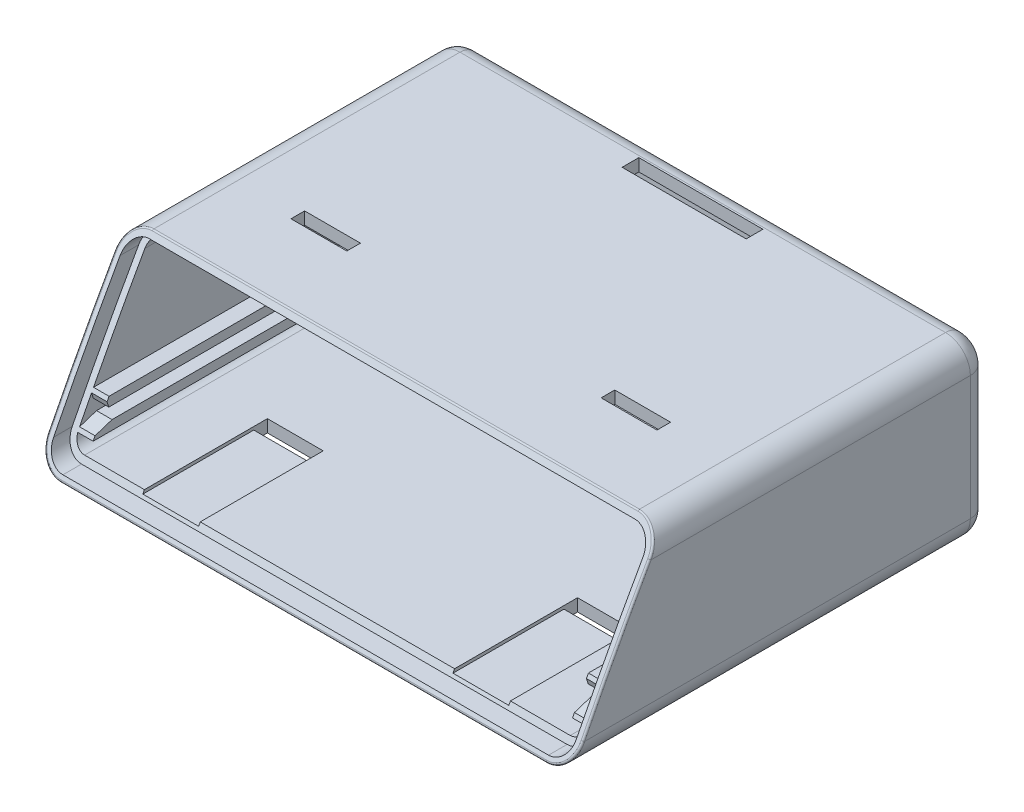
SolidWorks part; units mm, degrees
ref_plane "Front Plane" through (0, 0, 0) normal (0, 0, 1) x (1, 0, 0)
ref_plane "Top Plane" through (0, 0, 0) normal (0, 1, 0) x (1, 0, 0)
ref_plane "Right Plane" through (0, 0, 0) normal (1, 0, 0) x (0, 0, -1)
sketch "Sketch1" plane through (0, 0, 0) normal (0, 1, 0) x (1, 0, 0)
  line L1 (-43.14, -33.75) -> (43.14, -33.75)
  line L2 (-43.14, -33.75) -> (-43.14, 33.75)
  line L3 (-43.14, 33.75) -> (43.14, 33.75)
  line L4 (43.14, -33.75) -> (43.14, 33.75)
  line L5 (-43.14, -33.75) -> (43.14, 33.75) construction
  line L6 (-43.14, 33.75) -> (43.14, -33.75) construction
  point P0 (0, 0)
  dimension "D1" = 67.5
  dimension "D2" = 86.28
extrude "Boss-Extrude1" add sketch "Sketch1" along normal blind 28
fillet "Fillet1" radius 4 4 edges at (43.14, 28, 0) (43.14, 0, 0) (-43.14, 0, 0) (-43.14, 28, 0)
shell "Shell1" thickness 2
sketch "Sketch2" plane through (-43.14, 0, 0) normal (-1, 0, 0) x (0, 0, 1)
  line L0 (-33.75, 28) -> (33.75, 28) construction
  line L1 (18.75, 28) -> (33.75, 28)
  line L2 (33.75, 28) -> (33.75, 0)
  arc A0 (33.75, 0) -> (18.75, 28) centre (-392.2189, -210.1797) ccw
  dimension "D1" = 15
  dimension "D2" = 475
extrude "Cut-Extrude1" cut sketch "Sketch2" against normal through all
sketch "Sketch3" plane through (0, 0, -33.75) normal (0, 0, -1) x (-1, 0, 0)
  line L0 (-7.15, 18.7) -> (7.15, 18.7)
  line L1 (-6.95, 18.5) -> (6.95, 18.5) construction
  line L2 (-6.95, 18.5) -> (-6.95, 2.2) construction
  line L3 (-6.95, 2.2) -> (6.95, 2.2) construction
  line L4 (6.95, 18.5) -> (6.95, 2.2) construction
  line L5 (7.15, 18.7) -> (7.15, 2)
  line L6 (-7.15, 2) -> (7.15, 2)
  line L7 (-7.15, 18.7) -> (-7.15, 2)
  line L8 (27.25, 17.2) -> (38.3, 17.2)
  line L9 (27.45, 17) -> (38.1, 17) construction
  line L10 (27.45, 17) -> (27.45, 3.35) construction
  line L11 (27.45, 3.35) -> (38.1, 3.35) construction
  line L12 (38.1, 17) -> (38.1, 3.35) construction
  line L13 (38.3, 17.2) -> (38.3, 3.15)
  line L14 (27.25, 3.15) -> (38.3, 3.15)
  line L15 (27.25, 17.2) -> (27.25, 3.15)
  dimension "D1" = 0.2
  dimension "D2" = 0.2
extrude "Cut-Extrude2" cut sketch "Sketch3" against normal up to surface (2 mm away) up to face at (0, 14, -31.75)
fillet "Fillet2" radius 3 8 edges at (41.9684, 26.8284, -33.75) (43.14, 14, -33.75) (41.9684, 1.1716, -33.75) (0, 0, -33.75) (-41.9684, 1.1716, -33.75) (-43.14, 14, -33.75) (-41.9684, 26.8284, -33.75) (0, 28, -33.75)
sketch "Sketch4" plane through (0, 0, -31.75) normal (0, 0, 1) x (1, 0, 0)
  line L0 (-7.15, 2) -> (7.15, 2)
  line L1 (-7.15, 1) -> (7.15, 1)
  line L2 (7.15, 1) -> (39.14, 1)
  line L3 (42.14, 4) -> (42.14, 24)
  line L4 (39.14, 27) -> (-39.14, 27)
  line L5 (-42.14, 24) -> (-42.14, 4)
  line L6 (-39.14, 1) -> (-7.15, 1)
  line L8 (-7.15, 18.7) -> (7.15, 18.7)
  line L9 (7.15, 18.7) -> (7.15, 2)
  line L10 (7.15, 2) -> (39.14, 2)
  line L11 (41.14, 4) -> (41.14, 24)
  line L12 (39.14, 26) -> (-39.14, 26)
  line L13 (-41.14, 24) -> (-41.14, 4)
  line L14 (-39.14, 2) -> (-7.15, 2)
  line L15 (-7.15, 2) -> (-7.15, 18.7)
  line L18 (7.15, 2) -> (39.14, 2)
  line L19 (41.14, 4) -> (41.14, 24)
  line L20 (39.14, 26) -> (-39.14, 26)
  line L21 (-41.14, 24) -> (-41.14, 4)
  line L22 (-39.14, 2) -> (-7.15, 2)
  arc A0 (39.14, 1) -> (42.14, 4) centre (39.14, 4) ccw
  arc A1 (42.14, 24) -> (39.14, 27) centre (39.14, 24) ccw
  arc A2 (-39.14, 27) -> (-42.14, 24) centre (-39.14, 24) ccw
  arc A3 (-42.14, 4) -> (-39.14, 1) centre (-39.14, 4) ccw
  arc A4 (39.14, 2) -> (41.14, 4) centre (39.14, 4) ccw
  arc A5 (41.14, 24) -> (39.14, 26) centre (39.14, 24) ccw
  arc A6 (-39.14, 26) -> (-41.14, 24) centre (-39.14, 24) ccw
  arc A7 (-41.14, 4) -> (-39.14, 2) centre (-39.14, 4) ccw
  arc A8 (39.14, 2) -> (41.14, 4) centre (39.14, 4) ccw
  arc A9 (41.14, 24) -> (39.14, 26) centre (39.14, 24) ccw
  arc A10 (-39.14, 26) -> (-41.14, 24) centre (-39.14, 24) ccw
  arc A11 (-41.14, 4) -> (-39.14, 2) centre (-39.14, 4) ccw
  dimension "D1" = 0
  dimension "D2" = 1
extrude "Cut-Extrude3" cut sketch "Sketch4" against normal offset from surface (19.4971 mm away) 3 from offset 80
fillet "Fillet3" radius 0.3 8 edges at (41.7842, 27.0013, 19.3272) (43.14, 14.064, 26.517) (41.4452, 0.7311, 33.3885) (0, 0, 33.75) (-42.0581, 1.2642, 33.1239) (-43.14, 14.064, 26.517) (-41.3892, 27.3077, 19.1504) (0, 28, 18.75)
sketch "Sketch5" plane through (0, 0, -31.75) normal (0, 0, 1) x (1, 0, 0)
  line L0 (41.14, 24) -> (41.14, 4) construction
  line L1 (41.14, 5.25) -> (38.64, 5.25)
  line L2 (41.14, 5.25) -> (41.14, 3.75)
  line L3 (41.14, 3.75) -> (38.64, 3.75)
  line L4 (38.64, 5.25) -> (38.64, 3.75)
  line L5 (34.8894, 7.05) -> (40.64, 7.05) construction
  line L6 (41.14, 7.25) -> (38.64, 7.25)
  line L7 (41.14, 7.25) -> (41.14, 8.75)
  line L8 (41.14, 8.75) -> (38.64, 8.75)
  line L9 (38.64, 7.25) -> (38.64, 8.75)
  line L10 (-40.64, 7.05) -> (40.64, 7.05) construction
  line L11 (40.64, 5.45) -> (34.7752, 5.45) construction
  line L12 (-40.64, 5.45) -> (40.64, 5.45) construction
  line L13 (-41.14, 4) -> (-41.14, 24) construction
  line L14 (-41.14, 8.75) -> (-38.64, 8.75)
  line L15 (-41.14, 8.75) -> (-41.14, 7.25)
  line L16 (-41.14, 7.25) -> (-38.64, 7.25)
  line L17 (-38.64, 8.75) -> (-38.64, 7.25)
  line L19 (-41.14, 5.25) -> (-38.64, 5.25)
  line L20 (-41.14, 5.25) -> (-41.14, 3.75)
  line L21 (-41.14, 3.75) -> (-38.64, 3.75)
  line L22 (-38.64, 5.25) -> (-38.64, 3.75)
  dimension "D1" = 0.2
  dimension "D2" = 0.2
  dimension "D3" = 1.5
  dimension "D4" = 2.5
extrude "Boss-Extrude2" add sketch "Sketch5" along normal up to surface (59.8691 mm away)
sketch "Sketch6" plane through (0, 28, 0) normal (0, 1, 0) x (1, 0, 0)
  line L0 (0, 0) -> (0, 30.75) construction
  line L1 (-28.5, -4.13) -> (-28.5, -5.93) construction
  line L2 (21.5, -4.13) -> (28.5, -4.13) construction
  line L3 (21.5, -4.13) -> (21.5, -5.93) construction
  line L4 (21.5, -5.93) -> (28.5, -5.93) construction
  line L5 (28.5, -4.13) -> (28.5, -5.93) construction
  line L6 (20.5, -3.93) -> (29.5, -3.93)
  line L7 (20.5, -3.93) -> (20.5, -6.13)
  line L8 (20.5, -6.13) -> (29.5, -6.13)
  line L9 (39.14, 30.75) -> (-39.14, 30.75) construction
  line L10 (29.5, -3.93) -> (29.5, -6.13)
  line L11 (-21.5, -5.93) -> (-28.5, -5.93) construction
  line L12 (-21.5, -4.13) -> (-21.5, -5.93) construction
  line L13 (-21.5, -4.13) -> (-28.5, -4.13) construction
  line L14 (-29.5, -3.93) -> (-29.5, -6.13)
  line L15 (-20.5, -6.13) -> (-29.5, -6.13)
  line L16 (-20.5, -3.93) -> (-20.5, -6.13)
  line L17 (-20.5, -3.93) -> (-29.5, -3.93)
  dimension "D1" = 0.2
  dimension "D2" = 0.2
  dimension "D3" = 1
  dimension "D4" = 1
extrude "Cut-Extrude4" cut sketch "Sketch6" against normal up to surface (2 mm away) up to face at (0, 26, -7.4237)
sketch "Sketch9" plane through (0, 0, 0) normal (0, -1, 0) x (1, 0, 0)
  line L0 (0, 0) -> (0, 16.9026) construction
  line L1 (-28.5, 11.93) -> (-21.5, 11.93) construction
  line L2 (-28.5, 11.93) -> (-28.5, 10.13) construction
  line L3 (-28.5, 10.13) -> (-21.5, 10.13) construction
  line L4 (-21.5, 11.93) -> (-21.5, 10.13) construction
  line L5 (-29.5, 12.13) -> (-20.5, 12.13)
  line L6 (-29.5, 12.13) -> (-29.5, 9.93)
  line L7 (-29.5, 9.93) -> (-20.5, 9.93)
  line L8 (-20.5, 12.13) -> (-20.5, 9.93)
  line L9 (39.14, 16.9026) -> (-39.14, 16.9026) construction
  line L10 (21.5, 11.93) -> (21.5, 10.13) construction
  line L11 (28.5, 10.13) -> (21.5, 10.13) construction
  line L12 (28.5, 11.93) -> (28.5, 10.13) construction
  line L13 (28.5, 11.93) -> (21.5, 11.93) construction
  line L14 (20.5, 12.13) -> (20.5, 9.93)
  line L15 (29.5, 9.93) -> (20.5, 9.93)
  line L16 (29.5, 12.13) -> (29.5, 9.93)
  line L17 (29.5, 12.13) -> (20.5, 12.13)
  dimension "D1" = 0.2
  dimension "D2" = 0.2
  dimension "D3" = 1
  dimension "D4" = 1
extrude "Cut-Extrude7" cut sketch "Sketch9" against normal up to surface (2 mm away) up to face at (3.9987, 2, -16.6017)
sketch "Sketch7" plane through (0, 28, 0) normal (0, 1, 0) x (1, 0, 0)
  line L0 (-39.14, 33.75) -> (39.14, 33.75) construction
  line L1 (-10, 30.15) -> (10, 30.15)
  line L2 (-10, 30.15) -> (-10, 27.75)
  line L3 (-10, 27.75) -> (10, 27.75)
  line L4 (10, 30.15) -> (10, 27.75)
  line L5 (0, 27.75) -> (0, 0) construction
  dimension "D1" = 3.6
  dimension "D2" = 2.4
  dimension "D3" = 20
extrude "Cut-Extrude5" cut sketch "Sketch7" against normal up to surface (2 mm away) up to face at (-25, 26, 5.03)
sketch "Sketch8" plane through (0, 0, 6.13) normal (0, 0, -1) x (-1, 0, 0)
  line L0 (-29.5, 26) -> (-20.5, 26) construction
  line L1 (-29.5, 26) -> (-20.5, 26)
  line L2 (29.5, 26.5) -> (20.5, 26.5)
  line L3 (-20.5, 26.5) -> (-29.5, 26.5)
  line L4 (20.5, 26) -> (29.5, 26)
  line L5 (29.5, 26) -> (29.5, 28)
  line L6 (29.5, 28) -> (20.5, 28)
  line L7 (20.5, 28) -> (20.5, 26)
  line L8 (20.5, 26) -> (29.5, 26)
  line L9 (29.5, 26) -> (29.5, 26.5)
  line L10 (-20.5, 26.5) -> (-20.5, 26)
  line L11 (20.5, 26.5) -> (20.5, 26)
  line L12 (-29.5, 26.5) -> (-29.5, 26)
  line L14 (-29.5, 26) -> (-20.5, 26)
  line L15 (-20.5, 26) -> (-20.5, 28)
  line L16 (-20.5, 28) -> (-29.5, 28)
  line L17 (-29.5, 28) -> (-29.5, 26)
  line L18 (-29.5, 26) -> (-20.5, 26)
  dimension "D3" = 0.5
  dimension "D4" = 0.5
  dimension "D1" = 0
  dimension "D2" = 0
extrude "Cut-Extrude6" cut sketch "Sketch8" against normal through all
sketch "Sketch10" plane through (0, 0, 12.13) normal (0, 0, -1) x (-1, 0, 0)
  line L0 (29.5, 1.5) -> (20.5, 1.5)
  line L1 (-20.5, 1.5) -> (-29.5, 1.5)
  line L4 (-20.5, 2) -> (-29.5, 2)
  line L5 (-29.5, 2) -> (-29.5, 0)
  line L6 (-29.5, 0) -> (-20.5, 0)
  line L7 (-20.5, 0) -> (-20.5, 2)
  line L8 (-20.5, 2) -> (-29.5, 2)
  line L9 (-29.5, 2) -> (-29.5, 1.5)
  line L11 (-20.5, 1.5) -> (-20.5, 2)
  line L12 (29.5, 2) -> (20.5, 2)
  line L13 (20.5, 2) -> (20.5, 0)
  line L14 (20.5, 0) -> (29.5, 0)
  line L15 (29.5, 0) -> (29.5, 2)
  line L16 (29.5, 2) -> (20.5, 2)
  line L17 (20.5, 2) -> (20.5, 1.5)
  line L19 (29.5, 1.5) -> (29.5, 2)
  dimension "D3" = 0.5
  dimension "D1" = 0
  dimension "D2" = 0
extrude "Cut-Extrude8" cut sketch "Sketch10" against normal through all
sketch "Sketch11" plane through (0, 0, -31.75) normal (0, 0, 1) x (1, 0, 0)
  line L0 (-38.3, 3.15) -> (-38.3, 17.2) construction
  line L1 (-41.14, 5.25) -> (-38.3, 5.25)
  line L2 (-41.14, 5.25) -> (-41.14, 7.25)
  line L3 (-41.14, 7.25) -> (-38.3, 7.25)
  line L4 (-38.3, 5.25) -> (-38.3, 7.25)
  line L5 (-41.14, 7.25) -> (-38.64, 7.25) construction
  line L7 (41.14, 5.25) -> (7.15, 5.25)
  line L8 (41.14, 5.25) -> (41.14, 7.25)
  line L9 (41.14, 7.25) -> (7.15, 7.25)
  line L10 (7.15, 5.25) -> (7.15, 7.25)
  line L11 (-27.25, 17.2) -> (-27.25, 3.15) construction
  line L12 (-27.25, 5.25) -> (-7.15, 5.25)
  line L13 (-27.25, 5.25) -> (-27.25, 7.25)
  line L14 (-27.25, 7.25) -> (-7.15, 7.25)
  line L16 (-7.15, 5.25) -> (-7.15, 7.25)
  line L17 (-7.15, 2) -> (-7.15, 18.7) construction
  line L18 (7.15, 18.7) -> (7.15, 2) construction
  line L19 (38.64, 7.25) -> (41.14, 7.25) construction
extrude "Boss-Extrude3" add sketch "Sketch11" along normal blind 0.5
chamfer "Chamfer1" distance 1 angle 45 4 edges at (39.89, 5.25, 28.1191) (39.89, 7.25, 27.0954) (-39.89, 7.25, 27.0954) (-39.89, 5.25, 28.1191)
sketch "Sketch12" plane through (0, 0, -30.15) normal (0, 0, 1) x (1, 0, 0)
  line L4 (10, 26) -> (10, 28)
  line L5 (10, 28) -> (-10, 28)
  line L6 (-10, 28) -> (-10, 26)
  line L7 (-10, 26) -> (10, 26)
  line L8 (10, 26) -> (10, 28)
  line L9 (10, 28) -> (-10, 28)
  line L10 (-10, 28) -> (-10, 26)
  line L11 (-10, 26) -> (10, 26)
  dimension "D1" = 0
extrude "Cut-Extrude9" cut sketch "Sketch12" against normal blind 0.3
